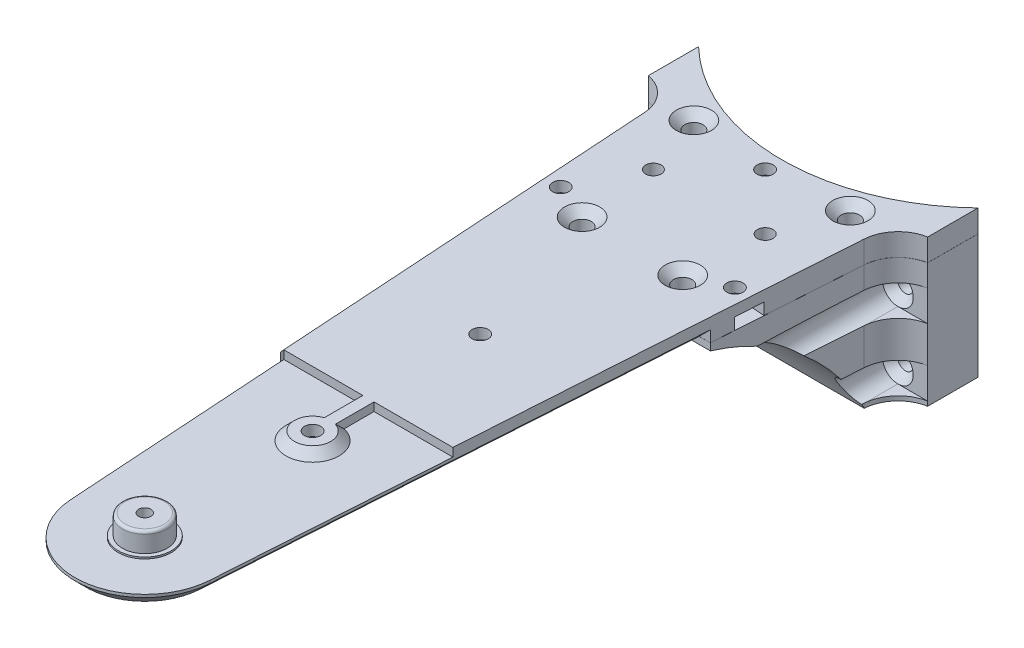
SolidWorks part; units mm, degrees
ref_plane "Front Plane" through (0, 0, 0) normal (0, 0, 1) x (1, 0, 0)
ref_plane "Top Plane" through (0, 0, 0) normal (0, 1, 0) x (1, 0, 0)
ref_plane "Right Plane" through (0, 0, 0) normal (1, 0, 0) x (0, 0, -1)
sketch "Sketch1" plane through (0, 0, 0) normal (0, 1, 0) x (1, 0, 0)
  line L0 (0, 0) -> (0, -150) construction
  line L1 (-22.2029, -1.4463) -> (-12.4736, -150.8125) construction
  line L2 (22.2029, -1.4462) -> (12.4736, -150.8125) construction
  line L3 (-12.4736, -150.8125) -> (-19.6328, -40.9037)
  line L4 (12.4736, -150.8125) -> (19.6328, -40.9037)
  line L5 (-25, -25.9037) -> (25, -25.9037) construction
  line L6 (-25, -25.9037) -> (-25, -34.9037)
  line L7 (25, -25.9037) -> (25, -34.9037)
  circle A0 centre (0, 0) radius 36 construction
  arc A1 (-12.4736, -150.8125) -> (12.4736, -150.8125) centre (0, -150) ccw
  circle A2 centre (0, 0) radius 19.5 construction
  circle A3 centre (0, 19.5) radius 2.75 construction
  circle A4 centre (0, 0) radius 22.25 construction
  arc A5 (-25, -25.9037) -> (25, -25.9037) centre (0, 0) ccw
  arc A6 (-25, -34.9037) -> (-19.6328, -40.9037) centre (-26.1442, -41.3278) cw
  arc A7 (25, -34.9037) -> (19.6328, -40.9037) centre (26.1442, -41.3278) ccw
  dimension "D1" = 72
  dimension "D3" = 25
  dimension "D4" = 39
  dimension "D5" = 5.5
  dimension "D2" = 150
  dimension "D6" = 50
  dimension "D7" = 9
  dimension "D8" = 15
extrude "Boss-Extrude1" add sketch "Sketch1" against normal blind 4
sketch "Sketch2" plane through (0, -4, 0) normal (0, -1, 0) x (1, 0, 0)
  line L0 (25, 34.9037) -> (25, 25.9037) construction
  line L1 (-25, 25.9037) -> (-25, 34.9037) construction
  line L2 (25, 34.9037) -> (25, 25.9037)
  line L3 (-25, 25.9037) -> (-25, 34.9037)
  line L4 (-19.6328, 40.9037) -> (19.6328, 40.9037)
  arc A0 (19.6328, 40.9037) -> (25, 34.9037) centre (26.1442, 41.3278) ccw construction
  arc A1 (25, 25.9037) -> (-25, 25.9037) centre (0, 0) ccw construction
  arc A2 (-25, 34.9037) -> (-19.6328, 40.9037) centre (-26.1442, 41.3278) ccw construction
  arc A3 (19.6328, 40.9037) -> (25, 34.9037) centre (26.1442, 41.3278) ccw
  arc A4 (25, 25.9037) -> (-25, 25.9037) centre (0, 0) ccw
  arc A5 (-25, 34.9037) -> (-19.6328, 40.9037) centre (-26.1442, 41.3278) ccw
extrude "Boss-Extrude2" add sketch "Sketch2" along normal offset from surface (22.2378 mm away) 26.2378 up to face at (0, 0, 65.6223)
ref_plane "Plane1" through (0, 0, 34.9037) normal (0, 0, 1) x (1, 0, 0)
fillet "Fillet2" radius 40 1 edges at (0, -4, 40.9037)
sketch "Sketch3" plane through (0, 0, 34.9037) normal (0, 0, 1) x (1, 0, 0)
  line L0 (25, 0) -> (-25, 0) construction
  line L1 (-19.6636, -22.6878) -> (19.6636, -22.6878) construction
  line L2 (-19.6636, -22.6878) -> (-19.6636, -10.6878) construction
  line L3 (-19.6636, -10.6878) -> (19.6636, -10.6878) construction
  line L4 (19.6636, -22.6878) -> (19.6636, -10.6878) construction
  line L5 (-19.6636, -22.6878) -> (19.6636, -10.6878) construction
  line L6 (-19.6636, -10.6878) -> (19.6636, -22.6878) construction
  line L7 (-19.6636, -7.9378) -> (-25, -7.9378)
  line L8 (-25, -7.9378) -> (-25, -13.4378)
  line L9 (-25, -13.4378) -> (-19.6636, -13.4378)
  line L10 (-25, -26.2378) -> (-25, 0) construction
  line L11 (0, -16.6878) -> (-25, -16.6878) construction
  line L12 (-25, -25.4378) -> (-25, -19.9378)
  line L13 (-25, -19.9378) -> (-19.6636, -19.9378)
  line L14 (-19.6636, -25.4378) -> (-25, -25.4378)
  line L15 (0, -16.6878) -> (0, 0) construction
  line L16 (19.6636, -25.4378) -> (25, -25.4378)
  line L17 (25, -19.9378) -> (19.6636, -19.9378)
  line L18 (25, -25.4378) -> (25, -19.9378)
  line L19 (25, -13.4378) -> (19.6636, -13.4378)
  line L20 (25, -7.9378) -> (25, -13.4378)
  line L21 (19.6636, -7.9378) -> (25, -7.9378)
  arc A0 (-19.6636, -13.4378) -> (-19.6636, -7.9378) centre (-19.6636, -10.6878) ccw
  arc A4 (-19.6636, -19.9378) -> (-19.6636, -25.4378) centre (-19.6636, -22.6878) cw
  arc A5 (19.6636, -19.9378) -> (19.6636, -25.4378) centre (19.6636, -22.6878) ccw
  arc A6 (19.6636, -13.4378) -> (19.6636, -7.9378) centre (19.6636, -10.6878) cw
  point P0 (0, -16.6878)
  dimension "D4" = 5.5
  dimension "D1" = 10.6878
  dimension "D2" = 12
  dimension "D3" = 39.3272
extrude "Cut-Extrude1" cut sketch "Sketch3" along normal through all
chamfer "Chamfer1" [suppressed] distance 2.75 angle 60
hole_wizard "CSK for M2.5 Flat Head Machine Screw1" positions "Sketch5" profile "Sketch6" countersink size "M2.5" standard "ANSI Metric" end condition through all
sketch "Sketch5" plane through (0, 0, 34.9037) normal (0, 0, 1) x (1, 0, 0)
  point P0 (19.6636, -22.6878)
  point P3 (-19.6636, -22.6878)
  point P6 (-19.6636, -10.6878)
  point P9 (19.6636, -10.6878)
sketch "Sketch6" plane through (19.6636, -22.6878, 34.9037) normal (1, 0, 0) x (0, -1, 0)
  line L0 (0, 0) -> (0, 9)
  line L1 (0, 9) -> (1.4, 9)
  line L2 (1.4, 9) -> (1.4, 1.35)
  line L3 (1.4, 1.35) -> (2.75, 0)
  line L5 (2.75, 0) -> (0, 0)
  line L6 (-1.4, 1.35) -> (-2.75, 0) construction
  line L11 (0, -6.35) -> (0, 107.95) construction
  dimension "Thru Hole Dia." = 2.8
  dimension "Thru Hole Depth" = 9
  dimension "Near C'Sink Dia." = 5.5
  dimension "Near C'Sink Angle" = 90
sketch "Sketch8" plane through (0, 0, 0) normal (0, 1, 0) x (1, 0, 0)
  line L1 (1.0164, -92.5616) -> (1.0209, -117.4381) construction
  line L2 (-0.9836, -92.5619) -> (-0.9791, -117.4384) construction
  line L3 (15.1322, -109.9973) -> (15.1322, -176.6324)
  line L4 (15.1322, -176.6324) -> (-15.0896, -176.6324)
  line L5 (-15.0896, -176.6324) -> (-15.0896, -109.9973)
  line L29 (-0.9805, -109.9973) -> (-0.9791, -117.4384)
  line L30 (1.0195, -109.9973) -> (1.0209, -117.4381)
  line L31 (1.0195, -109.9973) -> (15.1322, -109.9973)
  line L72 (-15.0896, -109.9973) -> (-0.9805, -109.9973)
  arc A4 (-0.9791, -117.4384) -> (1.0209, -117.4381) centre (0.0213, -120) ccw construction
  arc A8 (-0.9791, -117.4384) -> (1.0209, -117.4381) centre (0.0213, -120) ccw
  point P0 (0.0213, -176.6324)
  dimension "D2" = 5.5
extrude "Cut-Extrude3" cut sketch "Sketch8" against normal blind 1.5
sketch "Sketch9" plane through (0, -4, 0) normal (0, -1, 0) x (1, 0, 0)
  line L0 (-17.2982, 76.7436) -> (17.2982, 76.7436)
  line L1 (17.2982, 76.7436) -> (17.9496, 66.7436)
  line L2 (17.9496, 66.7436) -> (-17.9496, 66.7436)
  line L3 (-17.9496, 66.7436) -> (-17.2982, 76.7436)
  line L4 (-17.2982, 76.7436) -> (-12.4736, 150.8125) construction
  line L5 (12.4736, 150.8125) -> (17.2982, 76.7436) construction
  dimension "D1" = 10
extrude "Cut-Extrude4" cut sketch "Sketch9" along normal through all
sketch "Sketch11" plane through (0, -4, 0) normal (0, -1, 0) x (1, 0, 0)
  circle A0 centre (0, 0) radius 161
extrude "Cut-Extrude5" cut sketch "Sketch11" along normal blind 0.01
sketch "Sketch12" plane through (0, 0, 0) normal (0, 1, 0) x (1, 0, 0)
  line L0 (-17.9496, -66.7436) -> (17.9496, -66.7436) construction
  line L1 (-17.9496, -66.7436) -> (17.9496, -66.7436) construction
  line L3 (-9, -62.7436) -> (9, -62.7436) construction
  line L4 (-9, -62.7436) -> (-14, -37.7436) construction
  line L5 (-14, -37.7436) -> (14, -37.7436) construction
  line L6 (9, -62.7436) -> (14, -37.7436) construction
  line L7 (-9, -62.7436) -> (14, -37.7436) construction
  line L8 (-14, -37.7436) -> (9, -62.7436) construction
  circle A0 centre (-14, -37.7436) radius 1.65
  circle A1 centre (14, -37.7436) radius 1.65
  circle A2 centre (-9, -62.7436) radius 1.65
  circle A3 centre (9, -62.7436) radius 1.65
  point P2 (0, -52.961)
  point P15 (0, -62.7436)
  dimension "D1" = 3.3
  dimension "D2" = 4
  dimension "D3" = 28
  dimension "D4" = 25
  dimension "D5" = 18
extrude "Cut-Extrude6" cut sketch "Sketch12" against normal blind 8.25
ref_plane "Plane2" through (0, -5.2702, 0) normal (0, 1, 0) x (1, 0, 0)
sketch "Sketch13" plane through (0, -5.2702, 0) normal (0, 1, 0) x (1, 0, 0)
  line L0 (0, 0) -> (0, -36) construction
  line L1 (-11.75, -59.9936) -> (-6.25, -59.9936)
  line L2 (-11.75, -59.9936) -> (-11.75, -65.4936)
  line L3 (-11.75, -65.4936) -> (-6.25, -65.4936) construction
  line L4 (-6.25, -59.9936) -> (-6.25, -65.4936)
  line L5 (-11.75, -59.9936) -> (-6.25, -65.4936) construction
  line L6 (-11.75, -65.4936) -> (-6.25, -59.9936) construction
  line L7 (-6.25, -65.4936) -> (-6.25, -66.7436)
  line L8 (-17.9496, -66.7436) -> (17.9496, -66.7436) construction
  line L9 (-6.25, -66.7436) -> (-11.75, -66.7436)
  line L10 (-11.75, -66.7436) -> (-11.75, -65.4936)
  line L11 (6.25, -66.7436) -> (11.75, -66.7436)
  line L12 (6.25, -65.4936) -> (6.25, -66.7436)
  line L13 (6.25, -59.9936) -> (6.25, -65.4936)
  line L14 (11.75, -59.9936) -> (6.25, -59.9936)
  line L15 (11.75, -59.9936) -> (11.75, -65.4936)
  line L16 (11.75, -66.7436) -> (11.75, -65.4936)
  arc A0 (-25, -25.9037) -> (25, -25.9037) centre (0, 0) ccw construction
  point P0 (-9, -62.7436)
  dimension "D1" = 5.5
extrude "Cut-Extrude7" cut sketch "Sketch13" against normal blind 8.5
sketch "Sketch14" plane through (0, -8.25, 0) normal (0, 1, 0) x (1, 0, 0)
  line L0 (0, 0) -> (0, -36) construction
  line L1 (-14, -37.7436) -> (0, 0) construction
  line L2 (-15.681, -34.0804) -> (-10.3368, -36.0627) construction
  line L3 (-15.681, -34.0804) -> (-17.6632, -39.4246)
  line L4 (-17.6632, -39.4246) -> (-12.319, -41.4069)
  line L5 (-10.3368, -36.0627) -> (-12.319, -41.4069)
  line L6 (-15.681, -34.0804) -> (-12.319, -41.4069) construction
  line L7 (-17.6632, -39.4246) -> (-10.3368, -36.0627) construction
  line L8 (-15.681, -34.0804) -> (-15.1525, -32.6558)
  line L9 (-15.1525, -32.6558) -> (-9.8083, -34.6381)
  line L10 (-9.8083, -34.6381) -> (-10.3368, -36.0627)
  line L11 (15.1525, -32.6558) -> (9.8083, -34.6381)
  line L12 (15.681, -34.0804) -> (15.1525, -32.6558)
  line L13 (15.681, -34.0804) -> (17.6632, -39.4246)
  line L14 (17.6632, -39.4246) -> (12.319, -41.4069)
  line L15 (10.3368, -36.0627) -> (12.319, -41.4069)
  line L16 (9.8083, -34.6381) -> (10.3368, -36.0627)
  arc A0 (-25, -25.9037) -> (25, -25.9037) centre (0, 0) ccw construction
  point P6 (-14, -37.7436)
  dimension "D1" = 5.7
extrude "Cut-Extrude8" cut sketch "Sketch14" along normal blind 2
hole_wizard "CSK for M3 Flat Head Machine Screw1" positions "Sketch15" profile "Sketch16" countersink size "M3" standard "ANSI Metric"
sketch "Sketch15" plane through (0, 0, 0) normal (0, 1, 0) x (1, 0, 0)
  point P0 (-14, -37.7436)
  point P3 (14, -37.7436)
  point P6 (9, -62.7436)
  point P9 (-9, -62.7436)
sketch "Sketch16" plane through (-14, 0, 37.7436) normal (1, 0, 0) x (0, 0, 1)
  line L0 (0, 0) -> (0, 8.9914)
  line L1 (0, 8.9914) -> (1.65, 8)
  line L2 (1.65, 8) -> (1.65, 1.5)
  line L3 (1.65, 1.5) -> (3.15, 0)
  line L5 (3.15, 0) -> (0, 0)
  line L6 (-1.65, 1.5) -> (-3.15, 0) construction
  line L10 (0, 8.9914) -> (-1.65, 8) construction
  line L11 (0, -6.35) -> (0, 107.95) construction
  dimension "Hole Dia." = 3.3
  dimension "Hole Depth" = 8
  dimension "Near C'Sink Dia." = 6.3
  dimension "Near C'Sink Angle" = 90
  dimension "Drill Angle" = 118
sketch "Sketch18" plane through (0, -4, 0) normal (0, -1, 0) x (1, 0, 0)
  circle A1 centre (0.0071, 39) radius 2.75
  circle A2 centre (0.0071, 39) radius 2.75 construction
  circle A3 centre (0.016, 90) radius 2.8 construction
  arc A5 (1.0209, 117.4381) -> (-0.9791, 117.4384) centre (0.0213, 120) ccw construction
  circle A9 centre (-15.5725, 60.0029) radius 1.45
  circle A11 centre (-15.5725, 60.0029) radius 2.75
  circle A12 centre (-15.5725, 60.0029) radius 2.75 construction
  circle A13 centre (15.5944, 59.9971) radius 1.45
  circle A15 centre (0.0071, 39) radius 1.45
  circle A17 centre (15.5944, 59.9971) radius 2.75
  circle A18 centre (15.5944, 59.9971) radius 2.75 construction
  arc A19 (1.0209, 117.4381) -> (-0.9791, 117.4384) centre (0.0213, 120) ccw construction
  circle A20 centre (0.0213, 120) radius 1.45
  circle A21 centre (0.016, 90) radius 2.8 construction
  circle A22 centre (0.016, 90) radius 1.45
  dimension "D2" = 2.9
  dimension "D1" = 0
  dimension "D6" = 0
  dimension "D9" = 0
extrude "Cut-Extrude9" cut sketch "Sketch18" against normal through all
sketch "Sketch19" plane through (0, -4, 0) normal (0, -1, 0) x (1, 0, 0)
  line L1 (1.4503, 122.475) -> (-1.4076, 122.475)
  line L2 (-1.4076, 122.475) -> (-2.8366, 120)
  line L3 (-2.8366, 120) -> (-1.4076, 117.525)
  line L4 (-1.4076, 117.525) -> (1.4503, 117.525)
  line L5 (1.4503, 117.525) -> (2.8792, 120)
  line L6 (2.8792, 120) -> (1.4503, 122.475)
  line L7 (1.4449, 92.475) -> (-1.413, 92.475)
  line L8 (-1.413, 92.475) -> (-2.8419, 90)
  line L9 (-2.8419, 90) -> (-1.413, 87.525)
  line L10 (-1.413, 87.525) -> (1.4449, 87.525)
  line L11 (1.4449, 87.525) -> (2.8739, 90)
  line L12 (2.8739, 90) -> (1.4449, 92.475)
  line L13 (-12.7206, 59.8171) -> (-13.9857, 62.3797)
  line L14 (-13.9857, 62.3797) -> (-16.8375, 62.5655)
  line L15 (-16.8375, 62.5655) -> (-18.4243, 60.1886) construction
  line L16 (-18.4243, 60.1886) -> (-17.1593, 57.626) construction
  line L17 (-17.1593, 57.626) -> (-14.3074, 57.4402)
  line L18 (-14.3074, 57.4402) -> (-12.7206, 59.8171)
  line L19 (2.4786, 37.5649) -> (2.4857, 40.4228)
  line L20 (2.4857, 40.4228) -> (0.0143, 41.8579)
  line L21 (0.0143, 41.8579) -> (-2.4643, 40.4351)
  line L22 (-2.4643, 40.4351) -> (-2.4714, 37.5772)
  line L23 (-2.4714, 37.5772) -> (0, 36.1421) construction
  line L24 (0, 36.1421) -> (2.4786, 37.5649) construction
  line L25 (0, 0) -> (0, 162.5) construction
  line L26 (-18.4243, 60.1886) -> (-15.5725, 60.0029) construction
  line L27 (-19.6328, 40.9037) -> (-12.4736, 150.8125) construction
  line L28 (-16.8375, 62.5655) -> (-18.2159, 62.6553)
  line L29 (-18.2159, 62.6553) -> (-18.5377, 57.7158)
  line L30 (-18.5377, 57.7158) -> (-17.1593, 57.626)
  line L31 (18.2159, 62.6553) -> (18.5377, 57.7158)
  line L32 (16.8375, 62.5655) -> (18.2159, 62.6553)
  line L33 (13.9857, 62.3797) -> (16.8375, 62.5655)
  line L34 (12.7206, 59.8171) -> (13.9857, 62.3797)
  line L35 (14.3074, 57.4402) -> (12.7206, 59.8171)
  line L36 (17.1593, 57.626) -> (14.3074, 57.4402)
  line L37 (18.5377, 57.7158) -> (17.1593, 57.626)
  line L38 (-2.4714, 37.5772) -> (-2.4714, 35.9151)
  line L39 (-2.4714, 35.9151) -> (2.4786, 35.9146)
  line L40 (2.4786, 35.9146) -> (2.4786, 37.5649)
  circle A0 centre (0.0213, 120) radius 2.475 construction
  circle A1 centre (0.016, 90) radius 2.475 construction
  circle A2 centre (-15.5725, 60.0029) radius 2.475 construction
  circle A3 centre (0.0071, 39) radius 2.475 construction
  arc A4 (12.4736, 150.8125) -> (-12.4736, 150.8125) centre (0, 150) ccw construction
  arc A5 (25, 25.9037) -> (-25, 25.9037) centre (0, 0) ccw construction
  circle A6 centre (0.0213, 120) radius 1.45 construction
  circle A7 centre (0.016, 90) radius 1.45 construction
  point P9 (0, 0)
  point P53 (0, 0)
  dimension "D1" = 4.95
extrude "Cut-Extrude10" cut sketch "Sketch19" against normal blind 2.1
sketch "Sketch20" plane through (0, -1.5, 0) normal (0, 1, 0) x (1, 0, 0)
  circle A0 centre (0, -150) radius 4.75
  dimension "D1" = 9.5
extrude "Boss-Extrude3" add sketch "Sketch20" along normal blind 0.3
sketch "Sketch21" plane through (0, -1.2, 0) normal (0, 1, 0) x (1, 0, 0)
  circle A0 centre (0, -150) radius 4
  dimension "D1" = 8
extrude "Boss-Extrude4" add sketch "Sketch21" along normal blind 3.5
fillet "Fillet4" radius 0.5 1 edges at (0, 2.3, 154)
sketch "Sketch22" plane through (0, 0, 0) normal (0, 1, 0) x (1, 0, 0)
  line L0 (0, 0) -> (0, -150) construction
  circle A0 centre (0, 0) radius 50 construction
  arc A1 (-25, -25.9037) -> (25, -25.9037) centre (0, 0) ccw construction
  circle A2 centre (10, -48.9898) radius 1.4
  circle A3 centre (10, -48.9898) radius 3.5 construction
  circle A4 centre (-10, -48.9898) radius 1.4
  dimension "D1" = 100
  dimension "D2" = 2.8
  dimension "D4" = 7
  dimension "D3" = 10
extrude "Cut-Extrude12" cut sketch "Sketch22" against normal through all contours A2 | A4
sketch "Sketch24" plane through (0, 2.3, 0) normal (0, -1, 0) x (1, 0, 0)
  circle A0 centre (0, 150) radius 1.1
  dimension "D1" = 2.2
extrude "Cut-Extrude13" cut sketch "Sketch24" along normal through all
ref_plane "Plane3" through (0, 0, 36) normal (0, 0, -1) x (-1, 0, 0)
sketch "Sketch25" plane through (0, 0, 36) normal (0, 0, -1) x (-1, 0, 0)
  line L0 (-19.6636, -22.6878) -> (19.6636, -22.6878) construction
  line L1 (0, 0) -> (0, -22.6878) construction
  line L2 (-14.13, -15.5878) -> (-10.13, -15.5878)
  line L3 (-14.13, -15.5878) -> (-14.13, -18.5878)
  line L4 (-14.13, -18.5878) -> (-10.13, -18.5878)
  line L5 (-10.13, -15.5878) -> (-10.13, -18.5878)
  line L6 (10.13, -15.5878) -> (10.13, -18.5878)
  line L7 (14.13, -18.5878) -> (10.13, -18.5878)
  line L8 (14.13, -15.5878) -> (14.13, -18.5878)
  line L9 (14.13, -15.5878) -> (10.13, -15.5878)
  dimension "D1" = 7.1
  dimension "D2" = 20.26
  dimension "D3" = 4
  dimension "D4" = 3
extrude "Boss-Extrude6" add sketch "Sketch25" along normal blind 3
chamfer "Chamfer2" distance 1.8 angle 45 2 edges at (-12.1512, -18.5878, 33.8873) (12.1512, -18.5878, 33.8873)
chamfer "Chamfer3" distance 2 angle 45 3 edges at (-15.3447, -4, 106.7339) (0, -4, 162.5) (15.3447, -4, 106.7339)
chamfer "Chamfer4" distance 2 angle 45 1 edges at (0.0218, -1.5, 122.75)
sketch "Sketch26" plane through (0, -4, 0) normal (0, -1, 0) x (1, 0, 0)
  line L0 (-18.2159, 62.6553) -> (-12.4736, 150.8125) construction
  line L1 (12.4736, 150.8125) -> (18.2159, 62.6553) construction
  line L2 (-18.2159, 62.6553) -> (-17.9496, 66.7436)
  line L3 (17.9496, 66.7436) -> (18.2159, 62.6553)
  line L4 (-17.9496, 66.7436) -> (17.9496, 66.7436) construction
  line L5 (-17.9496, 66.7436) -> (-15.9454, 66.7436)
  line L6 (18.2159, 62.6553) -> (16.2202, 62.5253)
  line L7 (16.2202, 62.5253) -> (15.9454, 66.7436)
  line L8 (-18.2159, 62.6553) -> (-16.2202, 62.5253)
  line L9 (-10.4778, 150.6825) -> (-16.2202, 62.5253) construction
  line L10 (-16.2202, 62.5253) -> (-15.9454, 66.7436)
  line L11 (15.9454, 66.7436) -> (17.9496, 66.7436)
extrude "Boss-Extrude7" add sketch "Sketch26" against normal up to surface (4 mm away) up to face at (-10, 0, 47.5898)
